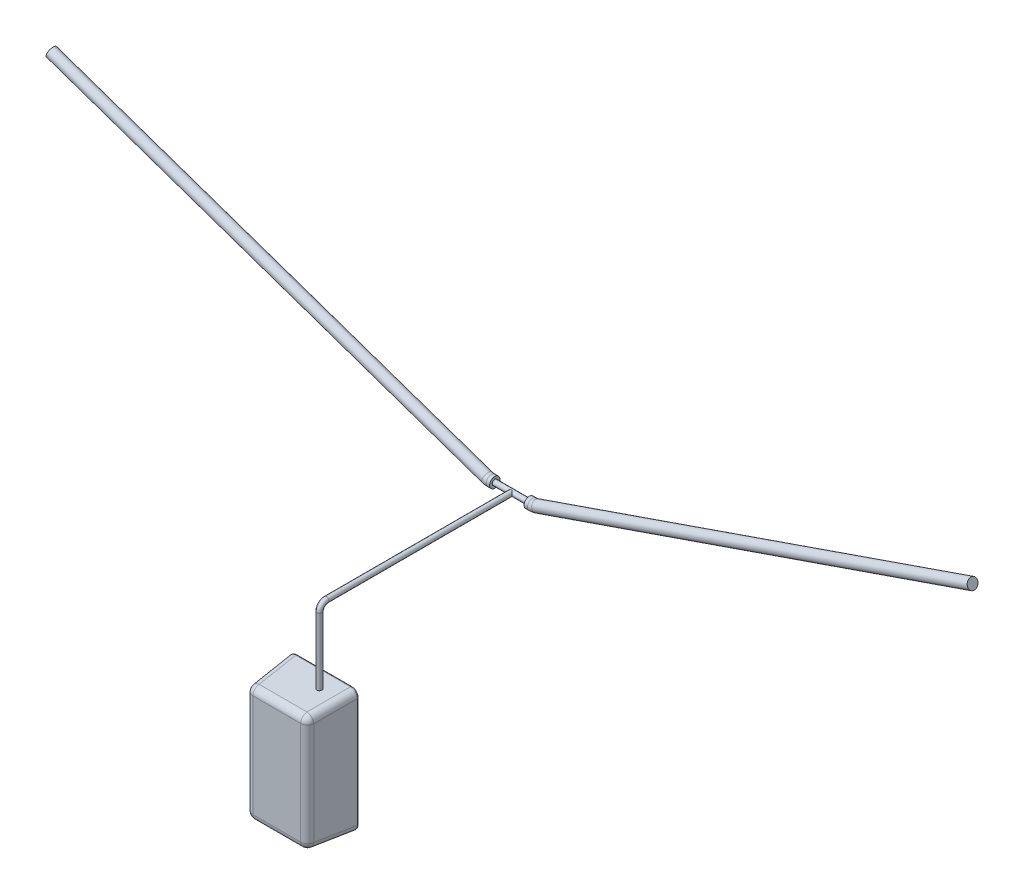
SolidWorks part; units mm, degrees
ref_plane "Front" through (0, 0, 0) normal (0, 0, 1) x (1, 0, 0)
ref_plane "Top" through (0, 0, 0) normal (0, 1, 0) x (1, 0, 0)
ref_plane "Right" through (0, 0, 0) normal (1, 0, 0) x (0, 0, -1)
sketch "Sketch1" plane through (0, 0, 0) normal (0, 0, 1) x (1, 0, 0)
  line L1 (-127, 228.6) -> (127, 228.6)
  line L2 (-127, 228.6) -> (-127, -228.6)
  line L3 (-127, -228.6) -> (127, -228.6)
  line L4 (127, 228.6) -> (127, -228.6)
  line L5 (-127, 228.6) -> (127, -228.6) construction
  line L6 (-127, -228.6) -> (127, 228.6) construction
  point P0 (0, 0)
  dimension "D1" = 254
  dimension "D2" = 457.2
extrude "Boss-Extrude1" add sketch "Sketch1" along normal blind 177.8 draft 5
fillet "Fillet1" radius 25.4 4 edges at (119.2223, -220.8223, 88.9) (-119.2223, -220.8223, 88.9) (119.2223, 220.8223, 88.9) (-119.2223, 220.8223, 88.9)
fillet "Fillet2" radius 25.4 8 edges at (-104.045, -205.645, 177.8) (-111.4445, 0, 177.8) (-104.045, 205.645, 177.8) (0, 213.0445, 177.8) (104.045, 205.645, 177.8) (111.4445, 0, 177.8) (104.045, -205.645, 177.8) (0, -213.0445, 177.8)
fillet "Fillet3" radius 6.35 8 edges at (119.6004, -221.2004, 0) (0, -228.6, 0) (-119.6004, -221.2004, 0) (-127, 0, 0) (-119.6004, 221.2004, 0) (0, 228.6, 0) (119.6004, 221.2004, 0) (127, 0, 0)
sketch "Sketch2" plane through (0, 0, 0) normal (0, 1, 0) x (1, 0, 0)
  line L0 (0, 0) -> (0, -69.85) construction
  line L1 (0, -69.85) -> (-76.2, -69.85) construction
  line L2 (0, -69.85) -> (25.4, -69.85) construction
  circle A0 centre (-76.2, -69.85) radius 3.175
  circle A1 centre (25.4, -69.85) radius 9.525
  dimension "D3" = 6.35
  dimension "D4" = 19.05
  dimension "D1" = 25.4
  dimension "D2" = 76.2
  dimension "D5" = 69.85
extrude "Boss-Extrude2" add sketch "Sketch2" against normal blind 279.4
sketch "Sketch3" plane through (0, 0, 0) normal (0, 1, 0) x (1, 0, 0)
  line L0 (0, 0) -> (0, -64.4508) construction
  line L1 (0, -64.4508) -> (44.45, -64.4508) construction
  circle A0 centre (44.45, -64.4508) radius 9.525
  dimension "D2" = 19.05
  dimension "D1" = 44.45
  dimension "D3" = 64.4508
extrude "Boss-Extrude3" add sketch "Sketch3" along normal blind 457.2
ref_axis "Axis1" through (44.45, 457.2, 64.4508) along (0, -1, 0)
ref_plane "Plane1" through (0, 0, 64.4508) normal (0, 0, -1) x (-1, 0, 0)
ref_plane "Plane2" through (44.45, 0, 0) normal (1, 0, 0) x (0, -1, 0)
sketch "Sketch5" plane through (44.45, 0, 0) normal (1, 0, 0) x (0, -1, 0)
  line L0 (-457.2, -64.4508) -> (-469.9, -64.4508)
  line L1 (-457.2, -54.9258) -> (-457.2, -73.9758) construction
  line L2 (-495.3, -39.0508) -> (-495.3, 646.7492)
  arc A0 (-469.9, -64.4508) -> (-495.3, -39.0508) centre (-469.9, -39.0508) cw
  dimension "D2" = 25.4
  dimension "D1" = 12.7
  dimension "D3" = 685.8
sketch "Sketch6" plane through (0, 457.2, 0) normal (0, 1, 0) x (1, 0, 0)
  circle A1 centre (44.45, -64.4508) radius 9.525
  circle A2 centre (44.45, -64.4508) radius 9.525
  dimension "D1" = 0
sweep "Sweep1" add profiles "Sketch6" path "Sketch5"
sketch "Sketch7" plane through (44.45, 0, 0) normal (1, 0, 0) x (0, -1, 0)
  line L0 (-485.775, 646.7492) -> (-504.825, 646.7492) construction
  circle A0 centre (-495.3, 646.7492) radius 9.525
extrude "Boss-Extrude4" add sketch "Sketch7" along normal mid plane 127
ref_axis "Axis2" through (107.95, 495.3, -646.7492) along (-1, 0, 0)
ref_plane "Plane3" through (0, 0, -646.7492) normal (0, 0, -1) x (-1, 0, 0)
sketch "Sketch8" plane through (0, 0, -646.7492) normal (0, 0, -1) x (-1, 0, 0)
  line L0 (19.05, 495.3) -> (31.75, 495.3)
  line L1 (19.05, 485.775) -> (19.05, 504.825) construction
  line L2 (48.3419, 498.0859) -> (1657.35, 1054.1)
  line L3 (1657.35, 1054.1) -> (1657.35, 495.3) construction
  line L4 (1657.35, 495.3) -> (31.75, 495.3) construction
  arc A0 (31.75, 495.3) -> (48.3419, 498.0859) centre (31.75, 546.1) ccw
  dimension "D1" = 50.8
  dimension "D2" = 1625.6
  dimension "D3" = 558.8
  dimension "D6" = 12.7
sketch "Sketch9" plane through (-19.05, 0, 0) normal (-1, 0, 0) x (0, 0, 1)
  circle A1 centre (-646.7492, 495.3) radius 19.05
  dimension "D1" = 38.1
sweep "Sweep3" add profiles "Sketch9" path "Sketch8"
mirror "Mirror1" about plane through (44.45, 0, 0) normal (1, 0, 0) of "Sweep3"
